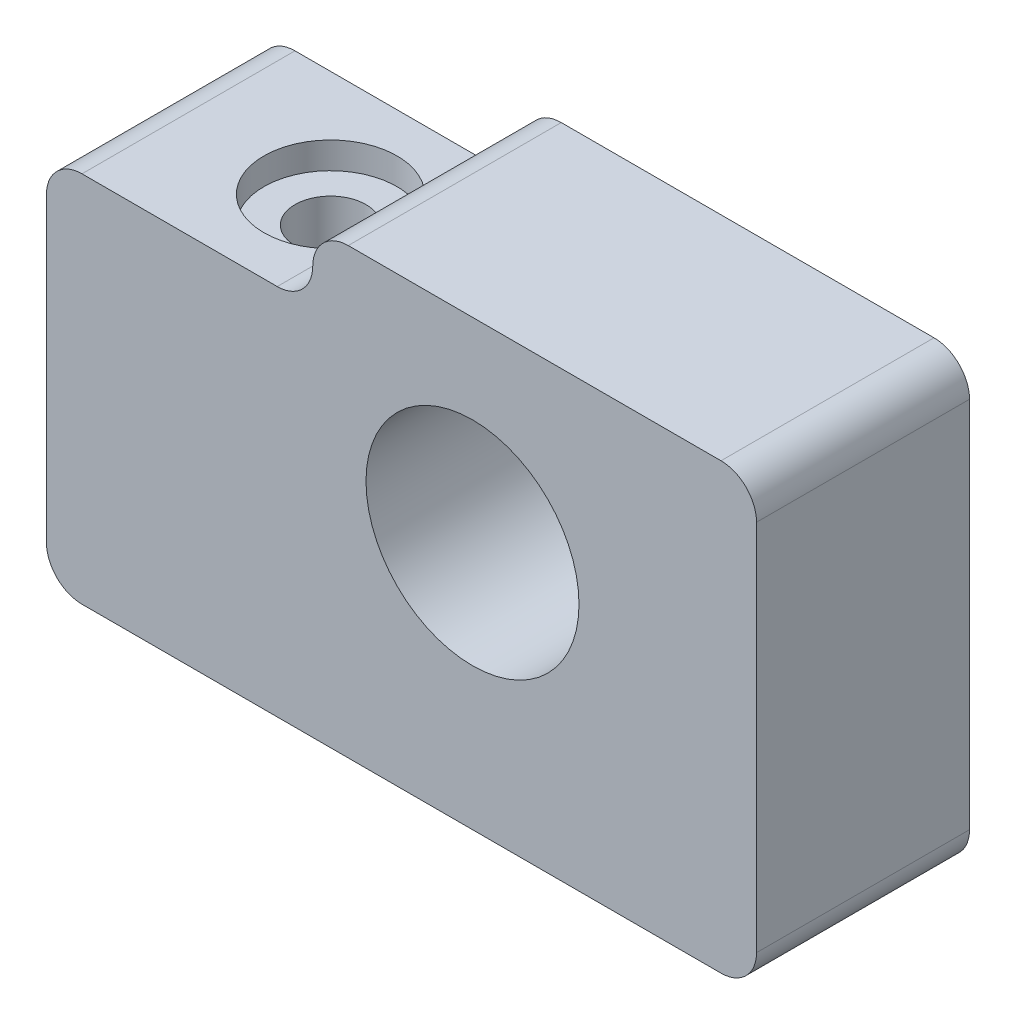
SolidWorks part; units mm, degrees
ref_plane "Front Plane" through (0, 0, 0) normal (0, 0, 1) x (1, 0, 0)
ref_plane "Top Plane" through (0, 0, 0) normal (0, 1, 0) x (1, 0, 0)
ref_plane "Right Plane" through (0, 0, 0) normal (1, 0, 0) x (0, 0, -1)
sketch "Sketch1" plane through (0, 0, 0) normal (0, 0, 1) x (1, 0, 0)
  line L0 (40, 21) -> (40, 25)
  line L1 (0, 0) -> (40, 0)
  line L2 (0, 0) -> (0, 21)
  line L3 (0, 21) -> (15, 21)
  line L4 (40, 0) -> (40, 21)
  line L5 (40, 25) -> (15, 25)
  line L6 (15, 25) -> (15, 21)
  dimension "D1" = 40
  dimension "D2" = 21
  dimension "D3" = 25
  dimension "D4" = 25
extrude "Boss-Extrude1" add sketch "Sketch1" along normal blind 12
sketch "Sketch2" plane through (0, 0, 12) normal (0, 0, 1) x (1, 0, 0)
  line L2 (0, 0) -> (40, 0) construction
  line L3 (0, 21) -> (0, 0) construction
  circle A0 centre (24, 14) radius 6
  dimension "D1" = 12
  dimension "D2" = 14
  dimension "D3" = 24
extrude "Cut-Extrude1" cut sketch "Sketch2" against normal up to next
sketch "Sketch3" plane through (0, 21, 0) normal (0, 1, 0) x (1, 0, 0)
  line L0 (0, -6) -> (15, -6) construction
  line L1 (0, -12) -> (0, 0) construction
  line L2 (15, -12) -> (15, 0) construction
  circle A0 centre (10, -6) radius 2
  dimension "D1" = 4
  dimension "D2" = 10
extrude "Cut-Extrude2" cut sketch "Sketch3" against normal up to next
sketch "Sketch4" plane through (0, 21, 0) normal (0, 1, 0) x (1, 0, 0)
  circle A0 centre (10, -6) radius 3.75
  dimension "D1" = 7.5
extrude "Cut-Extrude3" cut sketch "Sketch4" against normal blind 1.5
fillet "Fillet1" radius 2 6 edges at (0, 0, 6) (40, 0, 6) (40, 25, 6) (0, 21, 6) (15, 25, 6) (15, 21, 6)
